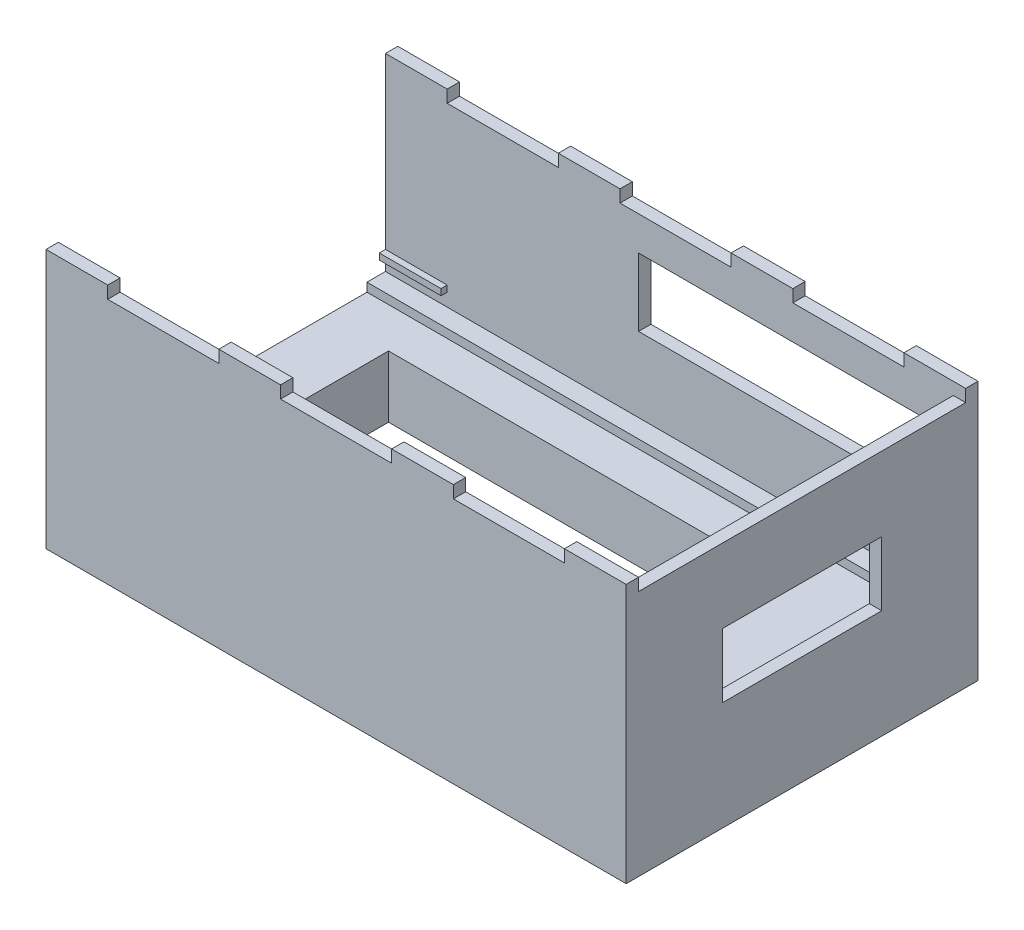
SolidWorks part; units mm, degrees
ref_plane "Front Plane" through (0, 0, 0) normal (0, 0, 1) x (1, 0, 0)
ref_plane "Top Plane" through (0, 0, 0) normal (0, 1, 0) x (1, 0, 0)
ref_plane "Right Plane" through (0, 0, 0) normal (1, 0, 0) x (0, 0, -1)
sketch "Sketch1" plane through (0, 0, 0) normal (0, 1, 0) x (1, 0, 0)
  line L1 (-30.298, 32.6459) -> (63.702, 32.6459)
  line L2 (-30.298, 32.6459) -> (-30.298, -24.3541)
  line L3 (-30.298, -24.3541) -> (63.702, -24.3541)
  line L4 (63.702, 32.6459) -> (63.702, -24.3541)
  dimension "D1" = 94
  dimension "D2" = 57
extrude "Boss-Extrude1" add sketch "Sketch1" along normal blind 10
sketch "Sketch2" plane through (0, 10, 0) normal (0, 1, 0) x (1, 0, 0)
  line L0 (-30.298, 32.6459) -> (63.702, 32.6459)
  line L1 (63.702, 32.6459) -> (63.702, -24.3541)
  line L2 (63.702, -24.3541) -> (-30.298, -24.3541)
  line L3 (-30.298, -24.3541) -> (-30.298, -22.3541)
  line L4 (-30.298, 32.6459) -> (-30.298, -24.3541) construction
  line L5 (-30.298, -22.3541) -> (61.702, -22.3541)
  line L6 (61.702, -22.3541) -> (61.702, 30.6459)
  line L7 (61.702, 30.6459) -> (-30.298, 30.6459)
  line L8 (-30.298, 30.6459) -> (-30.298, 32.6459)
  dimension "D1" = 2
  dimension "D2" = 2
  dimension "D3" = 2
extrude "Boss-Extrude2" add sketch "Sketch2" along normal blind 30
sketch "Sketch3" plane through (-30.298, 0, 0) normal (-1, 0, 0) x (0, 0, 1)
  line L0 (-30.6459, 40) -> (-30.6459, 10) construction
  line L1 (-30.6459, 10) -> (-27.6459, 10)
  line L2 (-30.6459, 10) -> (-30.6459, 11.4)
  line L3 (-30.6459, 11.4) -> (-27.6459, 11.4)
  line L4 (-27.6459, 10) -> (-27.6459, 11.4)
  line L5 (22.3541, 10) -> (19.3541, 10)
  line L6 (22.3541, 10) -> (22.3541, 11.4)
  line L7 (22.3541, 11.4) -> (19.3541, 11.4)
  line L8 (19.3541, 10) -> (19.3541, 11.4)
  line L9 (-30.6459, 14.5) -> (-29.6459, 14.5)
  line L10 (-30.6459, 14.5) -> (-30.6459, 13.5)
  line L11 (-30.6459, 13.5) -> (-29.6459, 13.5)
  line L12 (-29.6459, 14.5) -> (-29.6459, 13.5)
  line L13 (22.3541, 40) -> (22.3541, 10) construction
  line L14 (22.3541, 13.5) -> (21.3541, 13.5)
  line L15 (22.3541, 13.5) -> (22.3541, 14.5)
  line L16 (22.3541, 14.5) -> (21.3541, 14.5)
  line L17 (21.3541, 13.5) -> (21.3541, 14.5)
  dimension "D1" = 3
  dimension "D2" = 1.4
  dimension "D3" = 3
  dimension "D4" = 1.4
  dimension "D5" = 2.1
  dimension "D6" = 2.1
  dimension "D8" = 1
  dimension "D9" = 1
  dimension "D10" = 1
  dimension "D11" = 1
extrude "Boss-Extrude3" add sketch "Sketch3" against normal up to surface (92 mm away) contours L1 L4 L3 L2 | L5 L8 L7 L6 | L17 L16 L15 L14 up to face at (61.702, 25, -4.1459)
extrude "Boss-Extrude4" add sketch "Sketch3<3>" against normal blind 10 contours L12 L11 L10 L9
sketch "Sketch3<3>" plane through (-30.298, 0, 0) normal (-1, 0, 0) x (0, 0, 1) same geometry as "Sketch3"
sketch "Sketch4" plane through (0, 0, -32.6459) normal (0, 0, -1) x (-1, 0, 0)
  line L0 (-63.702, 40) -> (-63.702, 0) construction
  line L1 (-56.702, 34.5) -> (-10.702, 34.5)
  line L2 (-56.702, 34.5) -> (-56.702, 23.5)
  line L3 (-56.702, 23.5) -> (-10.702, 23.5)
  line L4 (-10.702, 34.5) -> (-10.702, 23.5)
  point P4 (-56.702, 29)
  dimension "D1" = 7
  dimension "D2" = 46
  dimension "D3" = 11
  dimension "D4" = 9
extrude "Cut-Extrude1" cut sketch "Sketch4" against normal blind 10
sketch "Sketch5" plane through (63.702, 0, 0) normal (1, 0, 0) x (0, 0, -1)
  line L1 (-8.7541, 28) -> (17.0459, 28)
  line L2 (-8.7541, 28) -> (-8.7541, 17.6)
  line L3 (-8.7541, 17.6) -> (17.0459, 17.6)
  line L4 (17.0459, 28) -> (17.0459, 17.6)
  line L5 (-24.3541, 40) -> (32.6459, 40) construction
  line L6 (4.1459, 40) -> (4.1459, 0) construction
  line L8 (-24.3541, 0) -> (32.6459, 0) construction
  point P10 (4.1459, 28)
  dimension "D1" = 0
  dimension "D2" = 25.8
  dimension "D3" = 12
  dimension "D4" = 10.4
extrude "Cut-Extrude2" cut sketch "Sketch5" against normal up to surface (2 mm away) up to face at (61.702, 16.8, 4.5207)
ref_plane "Plane5" through (0, 33, 0) normal (0, 1, 0) x (1, 0, 0)
sketch "Sketch7" plane through (0, 33, 0) normal (0, 1, 0) x (1, 0, 0)
  line L0 (61.702, -22.3541) -> (-30.298, -22.3541) construction
  line L1 (10.702, -22.3541) -> (61.702, -22.3541)
  line L2 (10.702, -22.3541) -> (10.702, -20.3541)
  line L3 (10.702, -20.3541) -> (59.702, -20.3541)
  line L4 (61.702, -22.3541) -> (61.702, -20.3541)
  line L5 (61.702, 27.6459) -> (61.702, -19.3541) construction
  line L6 (61.702, 30.6459) -> (61.702, -22.3541) construction
  line L8 (59.702, -20.3541) -> (59.702, 15.6459)
  line L9 (59.702, 15.6459) -> (61.702, 15.6459)
  line L10 (61.702, -20.3541) -> (61.702, 15.6459)
  dimension "D1" = 51
  dimension "D2" = 2
  dimension "D3" = 38
  dimension "D4" = 2
extrude "Boss-Extrude5" add sketch "Sketch7" against normal blind 2 contours L3 L8 L9 L10 L4 L1 L2
fillet "Fillet1" radius 1.5 2 edges at (59.702, 31, 2.3541) (35.202, 31, 20.3541) conic radius 3
ref_plane "Plane6" through (0, 34.8, 0) normal (0, 1, 0) x (1, 0, 0)
sketch "Sketch8" plane through (0, 34.8, 0) normal (0, 1, 0) x (1, 0, 0)
  line L1 (10.702, -20.3541) -> (59.702, -20.3541)
  line L2 (10.702, -20.3541) -> (10.702, -22.3541)
  line L3 (10.702, -22.3541) -> (61.702, -22.3541)
  line L4 (61.702, -20.3541) -> (61.702, -22.3541)
  line L5 (61.702, -22.3541) -> (59.702, -22.3541)
  line L6 (61.702, -22.3541) -> (61.702, 15.6459)
  line L7 (61.702, 15.6459) -> (59.702, 15.6459)
  line L8 (59.702, -20.3541) -> (59.702, 15.6459)
extrude "Boss-Extrude6" add sketch "Sketch8" along normal blind 1 contours L6 L7 L8 L1 L2 L3
sketch "Sketch9" plane through (0, 40, 0) normal (0, 1, 0) x (1, 0, 0)
  line L0 (-30.298, 30.6459) -> (61.702, 30.6459) construction
  line L1 (-30.298, 32.6459) -> (-20.298, 32.6459)
  line L2 (-30.298, 32.6459) -> (-30.298, 30.6459)
  line L3 (-30.298, 30.6459) -> (-20.298, 30.6459)
  line L4 (-20.298, 32.6459) -> (-20.298, 30.6459)
  line L5 (61.702, 30.6459) -> (-30.298, 30.6459) construction
  line L6 (-2.298, 30.6459) -> (7.702, 30.6459)
  line L7 (-2.298, 30.6459) -> (-2.298, 32.6459)
  line L8 (-2.298, 32.6459) -> (7.702, 32.6459)
  line L9 (7.702, 30.6459) -> (7.702, 32.6459)
  line L10 (63.702, 32.6459) -> (-30.298, 32.6459) construction
  line L11 (61.702, -22.3541) -> (-30.298, -22.3541) construction
  line L12 (25.702, 30.6459) -> (35.702, 30.6459)
  line L13 (25.702, 30.6459) -> (25.702, 32.6459)
  line L14 (25.702, 32.6459) -> (35.702, 32.6459)
  line L15 (35.702, 30.6459) -> (35.702, 32.6459)
  line L16 (53.702, 30.6459) -> (63.702, 30.6459)
  line L17 (53.702, 30.6459) -> (53.702, 32.6459)
  line L18 (53.702, 32.6459) -> (63.702, 32.6459)
  line L19 (63.702, 30.6459) -> (63.702, 32.6459)
  line L20 (-30.298, -24.3541) -> (-20.298, -24.3541)
  line L21 (-30.298, -24.3541) -> (-30.298, -22.3541)
  line L22 (-30.298, -22.3541) -> (-20.298, -22.3541)
  line L23 (-20.298, -24.3541) -> (-20.298, -22.3541)
  line L24 (-30.298, -24.3541) -> (63.702, -24.3541) construction
  line L25 (-2.298, -24.3541) -> (7.702, -24.3541)
  line L26 (-2.298, -24.3541) -> (-2.298, -22.3541)
  line L27 (-2.298, -22.3541) -> (7.702, -22.3541)
  line L28 (7.702, -24.3541) -> (7.702, -22.3541)
  line L29 (10.702, -22.3541) -> (61.702, -22.3541) construction
  line L30 (25.702, -24.3541) -> (35.702, -24.3541)
  line L31 (25.702, -24.3541) -> (25.702, -22.3541)
  line L32 (25.702, -22.3541) -> (35.702, -22.3541)
  line L33 (35.702, -24.3541) -> (35.702, -22.3541)
  line L35 (63.702, -24.3541) -> (53.702, -24.3541)
  line L36 (63.702, -24.3541) -> (63.702, -22.3541)
  line L37 (63.702, -22.3541) -> (53.702, -22.3541)
  line L38 (53.702, -24.3541) -> (53.702, -22.3541)
  dimension "D1" = 10
  dimension "D2" = 10
  dimension "D3" = 18
  dimension "D4" = 18
  dimension "D5" = 10
  dimension "D6" = 18
  dimension "D7" = 18
  dimension "D8" = 18
  dimension "D9" = 18
  dimension "D10" = 10
  dimension "D11" = 10
  dimension "D12" = 10
extrude "Boss-Extrude7" add sketch "Sketch9" along normal blind 2
sketch "Sketch10" plane through (0, 10, 0) normal (0, 1, 0) x (1, 0, 0)
  line L0 (-30.298, 4.1459) -> (61.702, 4.1459) construction
  line L1 (-20.298, 21.1459) -> (31.702, 21.1459)
  line L2 (-20.298, 21.1459) -> (-20.298, -12.8541)
  line L3 (-20.298, -12.8541) -> (31.702, -12.8541)
  line L4 (31.702, 21.1459) -> (31.702, -12.8541)
  line L5 (-30.298, 27.6459) -> (-30.298, -19.3541) construction
  line L6 (61.702, 30.6459) -> (61.702, -22.3541) construction
  point P10 (31.702, 4.1459)
  dimension "D1" = 34
  dimension "D2" = 0
  dimension "D3" = 52
  dimension "D4" = 10
extrude "Cut-Extrude3" cut sketch "Sketch10" against normal through all and the other way through all
